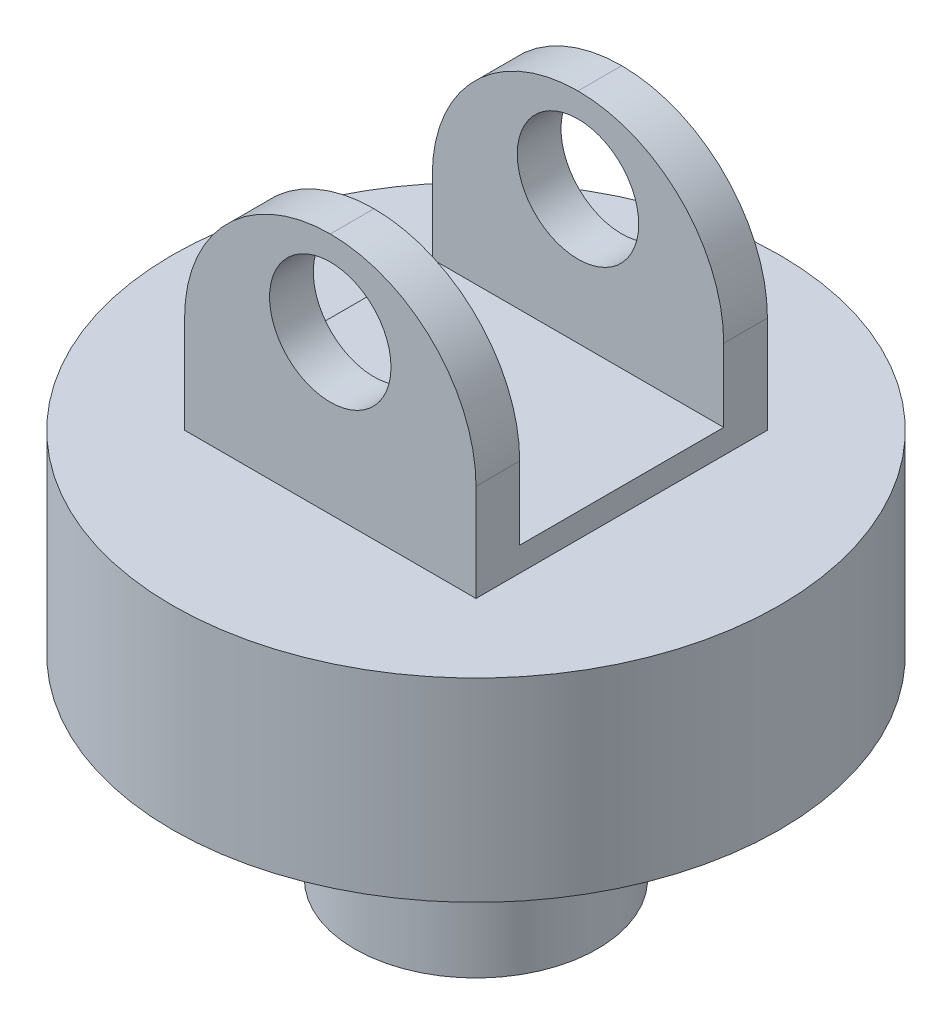
SolidWorks part; units mm, degrees
ref_plane "Front Plane" through (0, 0, 0) normal (0, 0, 1) x (1, 0, 0)
ref_plane "Top Plane" through (0, 0, 0) normal (0, 1, 0) x (1, 0, 0)
ref_plane "Right Plane" through (0, 0, 0) normal (1, 0, 0) x (0, 0, -1)
sketch "Sketch1" plane through (0, 0, 0) normal (0, 1, 0) x (1, 0, 0)
  circle A0 centre (0, 0) radius 125
  dimension "D1" = 250
extrude "Boss-Extrude1" add sketch "Sketch1" along normal blind 80
sketch "Sketch2" plane through (0, 80, 0) normal (0, 1, 0) x (1, 0, 0)
  circle A0 centre (0, 0) radius 50
  dimension "D1" = 100
extrude "Boss-Extrude2" add sketch "Sketch2" against normal blind 160
sketch "Sketch3" plane through (0, 80, 0) normal (0, 1, 0) x (1, 0, 0)
  line L1 (60, -60) -> (-60, -60)
  line L2 (60, -60) -> (60, 60)
  line L3 (60, 60) -> (-60, 60)
  line L4 (-60, -60) -> (-60, 60)
  line L5 (60, -60) -> (-60, 60) construction
  line L6 (60, 60) -> (-60, -60) construction
  point P0 (0, 0)
  dimension "D1" = 120
  dimension "D2" = 120
extrude "Boss-Extrude3" add sketch "Sketch3" along normal blind 100
sketch "Sketch4" plane through (0, 180, 0) normal (0, 1, 0) x (1, 0, 0)
  line L0 (60, -60) -> (60, 60) construction
  line L1 (-60, -42) -> (60, -42)
  line L2 (-60, -42) -> (-60, 42)
  line L3 (-60, 42) -> (60, 42)
  line L4 (60, -42) -> (60, 42)
  line L5 (-60, -42) -> (60, 42) construction
  line L6 (-60, 42) -> (60, -42) construction
  point P0 (0, 0)
  dimension "D1" = 84
extrude "Cut-Extrude1" cut sketch "Sketch4" against normal blind 90
fillet "Fillet1" radius 60 4 edges at (-60, 180, 51) (-60, 180, -51) (60, 180, -51) (60, 180, 51)
sketch "Sketch5" plane through (0, 0, 60) normal (0, 0, 1) x (1, 0, 0)
  line L2 (-60, 80) -> (60, 80) construction
  circle A0 centre (0, 145) radius 25
  dimension "D1" = 50
  dimension "D2" = 65
extrude "Cut-Extrude2" cut sketch "Sketch5" against normal blind 130
